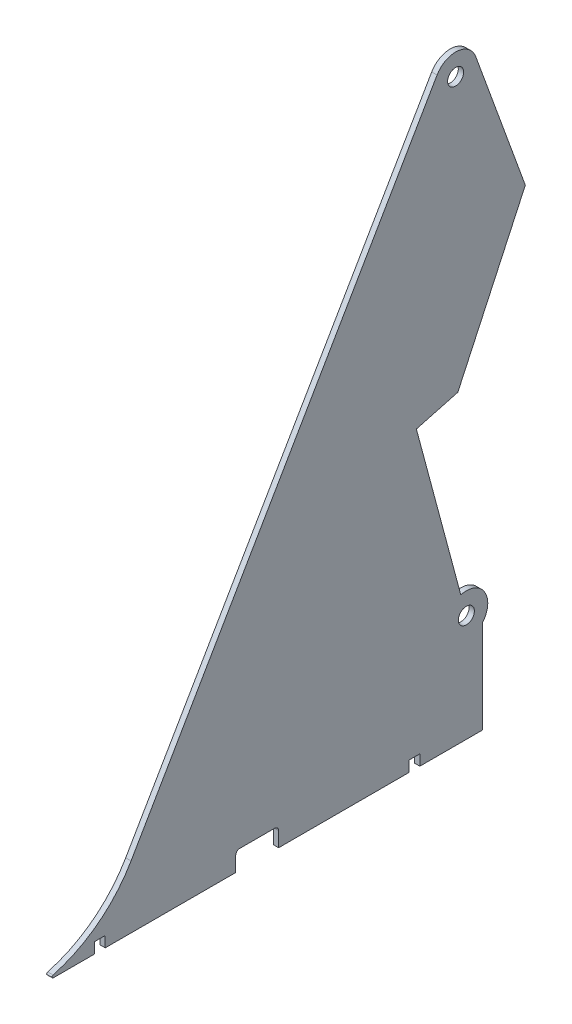
SolidWorks part; units mm, degrees
ref_plane "Front Plane" through (0, 0, 0) normal (0, 0, 1) x (1, 0, 0)
ref_plane "Top Plane" through (0, 0, 0) normal (0, 1, 0) x (1, 0, 0)
ref_plane "Right Plane" through (0, 0, 0) normal (1, 0, 0) x (0, 0, -1)
sketch "Sketch1" plane through (0, 0, 0) normal (1, 0, 0) x (0, 0, -1)
  line L0 (0, 0) -> (0, 55.0997)
  line L6 (-39.108, 173.9053) -> (-14.5735, 180.4793)
  line L7 (-14.5735, 180.4793) -> (25.4, 266.7)
  line L8 (25.4, 266.7) -> (-3.9421, 347.247)
  line L9 (-26.861, 349.2717) -> (-208.0116, 36.9339)
  line L10 (-254, 0) -> (0, 0)
  line L12 (-254.2054, 1.5605) -> (-207.9989, 13.9415) construction
  line L13 (-39.108, 173.9053) -> (-12.812, 75.7673)
  line L14 (-12.812, 75.7673) -> (13.738, 82.8813) construction
  arc A0 (-3.9421, 347.247) -> (-26.861, 349.2717) centre (-15.875, 342.9) ccw
  arc A1 (-254, 0) -> (-254.2054, 1.5605) centre (-254, 0.7937) cw
  arc A2 (-254.2054, 1.5605) -> (-208.0116, 36.9339) centre (-273.9274, 75.164) ccw
  arc A3 (0, 55.0997) -> (-12.812, 75.7673) centre (-9.525, 63.5) ccw
  point P14 (0, 0)
  dimension "D2" = 12.7
  dimension "D6" = 0.7937
  dimension "D7" = 76.2
  dimension "D12" = 12.7
  dimension "D1" = 15.875
  dimension "D3" = 342.9
  dimension "D4" = 25.4
  dimension "D5" = 101.6
  dimension "D8" = 254
  dimension "D9" = 15
  dimension "D10" = 9.525
  dimension "D11" = 63.5
  dimension "D13" = 76.2
  dimension "D14" = 25.4
  dimension "D15" = 15
extrude "Boss-Extrude1" add sketch "Sketch1" along normal blind 3.175
sketch "Sketch2" plane through (3.175, 0, 0) normal (1, 0, 0) x (0, 0, -1)
  line L16 (-146.05, 8.7909) -> (-146.05, -0.3034) construction
  line L17 (-123.0376, 11.1785) -> (-143.6624, 11.1785) construction
  line L18 (-120.65, -0.3034) -> (-120.65, 8.7909) construction
  line L19 (-146.05, 8.7909) -> (-146.05, 0)
  line L20 (-123.0376, 11.1785) -> (-143.6624, 11.1785)
  line L21 (-120.65, 0) -> (-120.65, 8.7909)
  line L23 (-37.0504, 0) -> (-37.0504, 6.35) construction
  line L24 (-43.4004, 0) -> (-37.0504, 0) construction
  line L25 (-146.05, 0) -> (-120.65, 0)
  line L26 (-254, 0) -> (0, 0) construction
  line L27 (-43.4004, 6.35) -> (-43.4004, 0) construction
  line L28 (-37.0504, 6.35) -> (-43.4004, 6.35) construction
  line L29 (-37.0504, 0) -> (-37.0504, 6.35)
  line L30 (-43.4004, 0) -> (-37.0504, 0)
  line L31 (-43.4004, 6.35) -> (-43.4004, 0)
  line L32 (-37.0504, 6.35) -> (-43.4004, 6.35)
  line L33 (-223.2996, 0) -> (-223.2996, 6.35) construction
  line L34 (-229.6496, 0) -> (-223.2996, 0) construction
  line L35 (-229.6496, 6.35) -> (-229.6496, 0) construction
  line L36 (-223.2996, 6.35) -> (-229.6496, 6.35) construction
  line L37 (-223.2996, 0) -> (-223.2996, 6.35)
  line L38 (-229.6496, 0) -> (-223.2996, 0)
  line L39 (-229.6496, 6.35) -> (-229.6496, 0)
  line L40 (-223.2996, 6.35) -> (-229.6496, 6.35)
  arc A0 (-143.6624, 11.1785) -> (-146.05, 8.7909) centre (-143.6624, 8.7909) ccw construction
  arc A1 (-120.65, 8.7909) -> (-123.0376, 11.1785) centre (-123.0376, 8.7909) ccw construction
  arc A2 (-143.6624, 11.1785) -> (-146.05, 8.7909) centre (-143.6624, 8.7909) ccw
  arc A3 (-120.65, 8.7909) -> (-123.0376, 11.1785) centre (-123.0376, 8.7909) ccw
extrude "Cut-Extrude1" cut sketch "Sketch2" against normal through all
sketch "Sketch3" plane through (3.175, 0, 0) normal (1, 0, 0) x (0, 0, -1)
  point P0 (-15.875, 342.9)
  point P4 (-9.525, 63.5)
hole_wizard "3/8 Clearance Hole1" positions "Sketch3" profile "Sketch4" hole size "3/8" standard "ANSI Inch" end condition up to next
sketch "Sketch4" plane through (3.175, 342.9, 15.875) normal (0, 1, 0) x (0, 0, -1)
  line L0 (0, 0) -> (0, 3.175)
  line L1 (0, 3.175) -> (4.7625, 3.175)
  line L2 (4.7625, 3.175) -> (4.7625, 0)
  line L5 (4.7625, 0) -> (0, 0)
  line L11 (0, -6.35) -> (0, 107.95) construction
  dimension "Thru Hole Dia." = 9.525
  dimension "Thru Hole Depth" = 3.175
sketch "Sketch5" plane through (3.175, 0, 0) normal (1, 0, 0) x (0, 0, -1)
  line L0 (-9.525, 63.5) -> (35.603, 40.174)
  line L1 (35.603, 40.174) -> (39.4095, 28.2222)
  line L2 (29.962, 43.0897) -> (-15.3934, 28.5628)
  line L3 (-15.875, 19.05) -> (-15.3934, 28.5628)
  line L4 (0, 0) -> (0, 55.0997) construction
  line L5 (-15.875, 19.05) -> (-28.647, 33.1843)
  line L6 (-28.647, 33.1843) -> (-54.7505, 169.5016)
  line L7 (50.8, 0) -> (50.8, 73.5762) construction
  point P7 (-28.647, 33.1843)
  dimension "D1" = 44.45
  dimension "D2" = 50.8
  dimension "D3" = 45
  dimension "D4" = 60.325
  dimension "D5" = 19.05
  dimension "D6" = 15.875
  dimension "D7" = 9.525
  dimension "D8" = 47.625
  dimension "D9" = 19.05
  dimension "D10" = 45
  dimension "D11" = 50.8
